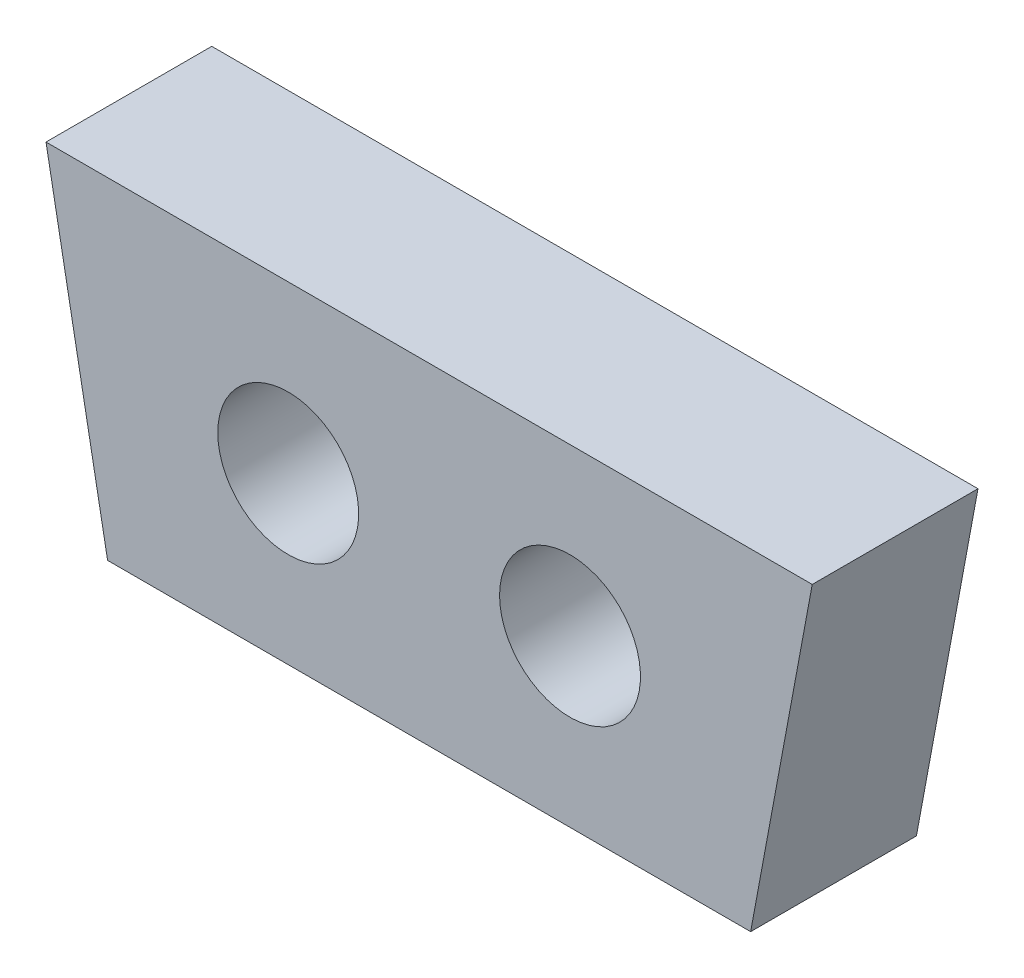
SolidWorks part; units mm, degrees
material "PLA Black"
ref_plane "Front" through (0, 0, 0) normal (0, 0, 1) x (1, 0, 0)
ref_plane "Top" through (0, 0, 0) normal (0, 1, 0) x (1, 0, 0)
ref_plane "Right" through (0, 0, 0) normal (1, 0, 0) x (0, 0, -1)
sketch "Sketch1" plane through (0, 0, 0) normal (0, 0, -1) x (1, 0, 0)
  line L0 (7.759, 4) -> (-7.759, 4)
  line L1 (-9.2451, -4) -> (9.2451, -4)
  line L2 (9.2451, -4) -> (7.759, 4)
  line L3 (-9.2451, -4) -> (-7.759, 4)
  line L4 (0, 8.8039) -> (0, -5.128) construction
  line L5 (-9.2451, -4) -> (9.2451, -4) construction
  line L6 (10.8682, 0) -> (-14.6589, 0) construction
  spline S0 degree 3 poles (9.2451, -4) (8.808, -2.0191) (8.4147, -0.0282) (7.743, 3.9732) (7.4652, 5.9821) (7.25, 8) knots 0 0 0 0 0.5 0.5 1 1 1 1 construction
  spline S3 degree 3 poles (-7.25, 8) (-7.4652, 5.9821) (-7.743, 3.9732) (-8.4147, -0.0282) (-8.808, -2.0191) (-9.2451, -4) knots 0 0 0 0 0.5 0.5 1 1 1 1 construction
extrude "Boss-Extrude1" add sketch "Sketch1" along normal blind 4
hole_wizard "M3 Clearance Hole1" positions "Sketch4" profile "Sketch3" hole size "M3" standard "DIN" end condition through all
sketch "Sketch4" plane through (0, 0, -4) normal (0, 0, -1) x (-1, 0, 0)
  circle A1 centre (-3.4, 0) radius 2.15 construction
  circle A2 centre (3.4, 0) radius 2.15 construction
  point P0 (-3.4, 0)
  point P2 (3.4, 0)
sketch "Sketch3" plane through (3.4, 0, -4) normal (1, 0, 0) x (0, 1, 0)
  line L0 (0, 0) -> (0, 4)
  line L1 (0, 4) -> (1.7, 4)
  line L2 (1.7, 4) -> (1.7, 0)
  line L5 (1.7, 0) -> (0, 0)
  line L11 (0, -6.35) -> (0, 107.95) construction
  dimension "Thru Hole Dia." = 3.4
  dimension "Thru Hole Depth" = 4
